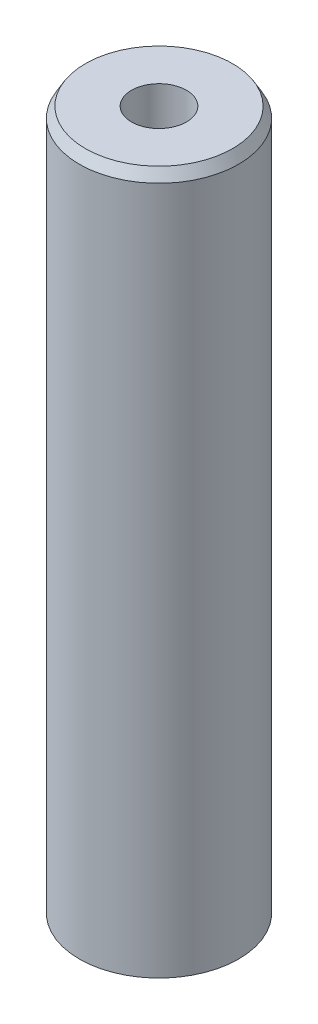
SolidWorks part; units mm, degrees
ref_plane "Front Plane" through (0, 0, 0) normal (0, 0, 1) x (1, 0, 0)
ref_plane "Top Plane" through (0, 0, 0) normal (0, 1, 0) x (1, 0, 0)
ref_plane "Right Plane" through (0, 0, 0) normal (1, 0, 0) x (0, 0, -1)
sketch "Sketch1" plane through (0, 0, 0) normal (0, 1, 0) x (1, 0, 0)
  circle A0 centre (0, 0) radius 25
  dimension "SHAFT_OD" = 50
extrude "Boss-Extrude1" add sketch "Sketch1" along normal blind 221.1298
sketch "Sketch2" plane through (0, 0, 0) normal (0, 1, 0) x (1, 0, 0)
  circle A0 centre (0, 0) radius 8.6274
  dimension "BORE_D" = 17.2547
extrude "Cut-Extrude1" cut sketch "Sketch2" along normal through all
chamfer "Chamfer1" distance 3.2942 angle 30 2 edges at (0, 221.1298, 25) (0, 0, 25) first distance on face at (0, 221.1298, 25) first distance on face at (0, 0, 8.6274)
